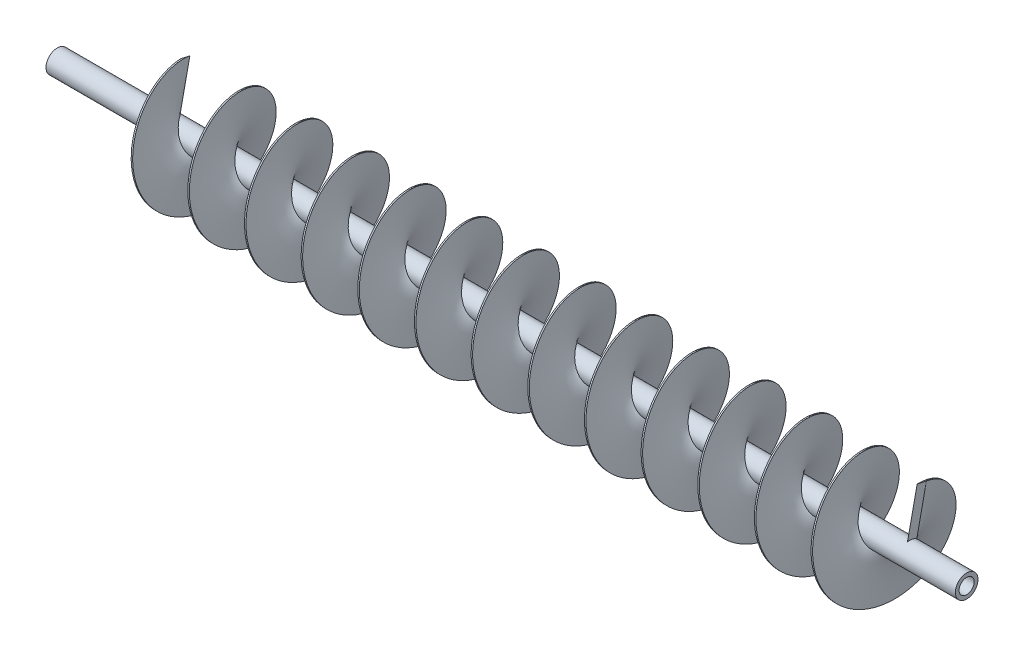
SolidWorks part; units mm, degrees
material "Brass"
ref_plane "Vorderansicht" through (0, 0, 0) normal (0, 0, 1) x (1, 0, 0)
ref_plane "Draufsicht" through (0, 0, 0) normal (0, 1, 0) x (1, 0, 0)
ref_plane "Seitenansicht" through (0, 0, 0) normal (1, 0, 0) x (0, 0, -1)
sketch "Skizze3" plane through (0, 0, 0) normal (1, 0, 0) x (0, 0, -1)
  circle A0 centre (0, 0) radius 6
  circle A1 centre (0, 0) radius 4
  dimension "D1" = 12
  dimension "D2" = 2
extrude "Aufsatz-Linear austragen1" add sketch "Skizze3" against normal blind 415 and the other way blind 51.5 separate body
ref_plane "Ref_of_Spiral" through (36.5, 0, 0) normal (1, 0, 0) x (0, 0, -1)
sketch "Skizze1" plane through (36.5, 0, 0) normal (1, 0, 0) x (0, 0, -1)
  circle A0 centre (0, 0) radius 4
  dimension "D1" = 8
curve "Spirale/Helix1" pitch 30 height 390 radius 4 centre (36.5, 0, 0) axis (-1, 0, 0) start towards (0, 0, -1)
sketch "Skizze2" plane through (0, 0, 0) normal (1, 0, 0) x (0, 0, -1)
  line L0 (19.3938, 0) -> (56.2084, 0) construction
  line L2 (3.1225, -2.5) -> (30, -2.5)
  line L4 (3.1225, 2.5) -> (30, 2.5)
  line L5 (30, -2.5) -> (30, 2.5)
  arc A1 (3.1225, -2.5) -> (3.1225, 2.5) centre (0, 0) ccw
  dimension "D1" = 30
  dimension "D3" = 5
sweep "Austragung1" add profiles "Skizze2" path "Spirale/Helix1"
sketch "Sketch1" plane through (51.5, 0, 0) normal (1, 0, 0) x (0, 0, -1)
  circle A0 centre (0, 0) radius 4
  circle A1 centre (0, 0) radius 6
extrude "Boss-Extrude1" add sketch "Sketch1" along normal blind 15
